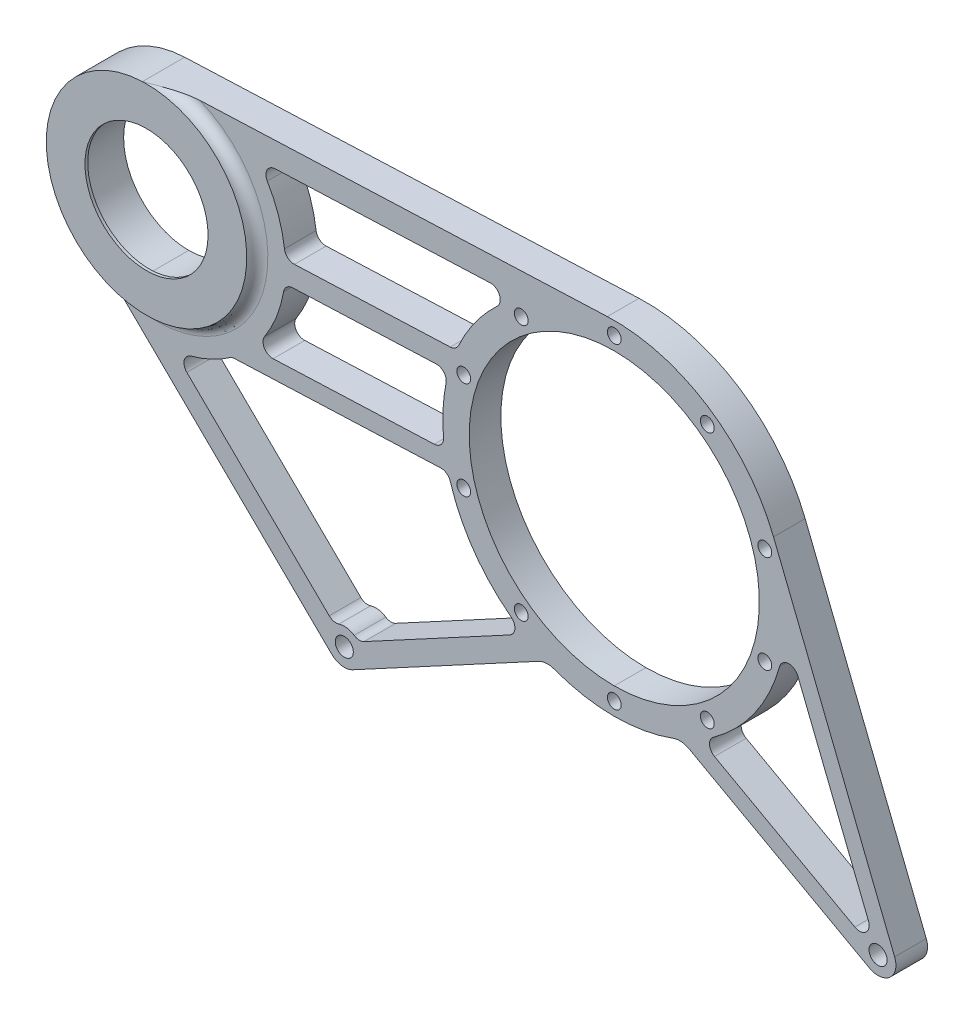
SolidWorks part; units mm, degrees
material "6061-T6 (SS)"
ref_plane "Front Plane" through (0, 0, 0) normal (0, 0, 1) x (1, 0, 0)
ref_plane "Top Plane" through (0, 0, 0) normal (0, 1, 0) x (1, 0, 0)
ref_plane "Right Plane" through (0, 0, 0) normal (1, 0, 0) x (0, 0, -1)
sketch "Sketch1" plane through (0, 0, 0) normal (0, 0, 1) x (1, 0, 0)
  line L0 (-114.3, 95.25) -> (-114.3, 107.95) construction
  line L1 (-280.8642, 163.1704) -> (-116.8043, 169.8118)
  line L2 (-304.7421, 101.1501) -> (-216.3071, 14.4521)
  line L3 (-13.0706, 21.4387) -> (-56.8054, 130.918)
  line L4 (-208.742, 13.3833) -> (-141.7118, 49.5504)
  line L5 (-22.1639, 13.4141) -> (-87.2342, 49.3665)
  circle A0 centre (-279.4, 127) radius 23.5
  circle A1 centre (-114.3, 95.25) radius 36 construction
  circle A2 centre (0, 0) radius 12.7 construction
  circle A3 centre (-228.6, 0) radius 12.7 construction
  circle A4 centre (-114.3, 107.95) radius 52.3875
  circle A5 centre (-19.05, 19.05) radius 3.2639
  circle A6 centre (-211.7995, 19.05) radius 3.2639
  circle A7 centre (-279.4, 127) radius 36.2
  arc A8 (-135.9521, 49.947) -> (-93.0137, 49.8118) centre (-114.3, 107.95) ccw
  arc A9 (-216.3071, 14.4521) -> (-208.742, 13.3833) centre (-211.7995, 19.05) ccw
  arc A10 (-22.1639, 13.4141) -> (-13.0706, 21.4387) centre (-19.05, 19.05) ccw
  arc A11 (-56.8054, 130.918) -> (-116.8043, 169.8118) centre (-114.3, 107.95) ccw
  arc A12 (-135.9521, 49.947) -> (-141.7118, 49.5504) centre (-138.3949, 43.4031) ccw
  arc A13 (-87.2342, 49.3665) -> (-93.0137, 49.8118) centre (-90.6122, 43.2526) ccw
  point P27 (-90.1176, 50.9555)
  point P28 (-138.831, 50.9555)
  dimension "D5" = 72
  dimension "D6" = 47
  dimension "D7" = 25.4
  dimension "D8" = 25.4
  dimension "D11" = 104.775
  dimension "D14" = 6.5278
  dimension "D15" = 6.5278
  dimension "D16" = 25.4
  dimension "D17" = 12.7
  dimension "D18" = 123.825
  dimension "D19" = 3.175
  dimension "D20" = 6.985
  dimension "D21" = 6.985
  dimension "D1" = 114.3
  dimension "D2" = 95.25
  dimension "D3" = 279.4
  dimension "D4" = 127
  dimension "D9" = 228.6
  dimension "D10" = 12.7
  dimension "D12" = 19.05
  dimension "D13" = 19.05
extrude "Boss-Extrude1" add sketch "Sketch1" along normal blind 11.43 contours A13 L5 A10 L3 A11 L1 A7 L2 A9 L4 A12 A8 A6 A5 A4 | A7 A0 region at (-168.693, 91.0379, 0) region at (-255.035, 152.3713, 0)
sketch "Sketch2" plane through (0, 0, 11.43) normal (0, 0, 1) x (1, 0, 0)
  circle A0 centre (-279.4, 127) radius 36.2
  circle A1 centre (-279.4, 127) radius 23.5
extrude "Boss-Extrude2" add sketch "Sketch2" along normal blind 3.81
fillet "Fillet1" radius 3.81 1 edges at (-245.6173, 113.9936, 11.43)
sketch "Sketch3" plane through (0, 0, 11.43) normal (0, 0, 1) x (1, 0, 0)
  line L0 (-114.3, 107.95) -> (-114.3, 165.1) construction
  circle A0 centre (-114.3, 107.95) radius 57.15 construction
  circle A1 centre (-114.3, 165.1) radius 2.5
  circle A2 centre (-80.7081, 154.1853) radius 2.5
  circle A3 centre (-59.9471, 125.6103) radius 2.5
  circle A4 centre (-59.9471, 90.2897) radius 2.5
  circle A5 centre (-80.7081, 61.7147) radius 2.5
  circle A6 centre (-114.3, 50.8) radius 2.5
  circle A7 centre (-147.8919, 61.7147) radius 2.5
  circle A8 centre (-168.6529, 90.2897) radius 2.5
  circle A9 centre (-168.6529, 125.6103) radius 2.5
  circle A10 centre (-147.8919, 154.1853) radius 2.5
  point P25 (-114.3, 107.95)
  dimension "D1" = 114.3
  dimension "D2" = 5
  dimension "D3" = 10
extrude "5mm Holes" cut sketch "Sketch3" against normal through all
sketch "Sketch4" plane through (0, 0, 15.24) normal (0, 0, 1) x (1, 0, 0)
  circle A0 centre (-279.4, 127) radius 22.225
  circle A1 centre (-279.4, 127) radius 23.5 construction
  circle A2 centre (-279.4, 127) radius 23.5
  dimension "D1" = 44.45
extrude "Boss-Extrude3" add sketch "Sketch4" against normal blind 1
sketch "Sketch5" plane through (0, 0, 11.43) normal (0, 0, 1) x (1, 0, 0)
  line L0 (-48.0193, 91.8071) -> (-22.5033, 27.9342)
  line L1 (-13.0706, 21.4387) -> (-56.8054, 130.918) construction
  line L2 (-78.1047, 51.5771) -> (-27.4356, 23.5816)
  line L3 (-22.1639, 13.4141) -> (-87.2342, 49.3665) construction
  line L4 (-236.7455, 156.0591) -> (-159.125, 159.2013)
  line L5 (-263.8382, 163.8596) -> (-116.8043, 169.8118) construction
  line L6 (-229.7856, 129.649) -> (-173.517, 131.9269)
  line L7 (-230.4174, 121.9972) -> (-178.6103, 124.0944)
  line L8 (-268.6449, 76.4329) -> (-217.2302, 26.028)
  line L9 (-204.6483, 24.2506) -> (-152.0143, 52.6499)
  line L10 (-292.5742, 89.2212) -> (-216.3071, 14.4521) construction
  line L11 (-208.742, 13.3833) -> (-141.7118, 49.5504) construction
  line L12 (-237.4937, 96.2899) -> (-179.3047, 98.6455)
  line L13 (-251.3498, 89.3738) -> (-177.0086, 92.3833)
  arc A0 (-175.0426, 119.9291) -> (-175.9673, 102.4457) centre (-114.3, 107.95) ccw construction
  circle A1 centre (-211.7995, 19.05) radius 6.4389 construction
  circle A2 centre (-19.05, 19.05) radius 6.4389 construction
  arc A3 (-54.6287, 91.4427) -> (-78.4387, 57.481) centre (-114.3, 107.95) cw
  arc A4 (-48.0193, 91.8071) -> (-54.6287, 91.4427) centre (-51.2626, 90.5115) ccw
  arc A5 (-27.4356, 23.5816) -> (-22.5033, 27.9342) centre (-25.7466, 26.6385) ccw
  arc A6 (-78.1047, 51.5771) -> (-78.4387, 57.481) centre (-76.4157, 54.634) cw
  arc A7 (-233.3928, 132.7086) -> (-253.1835, 88.7646) centre (-279.4, 127) ccw construction
  arc A8 (-292.5742, 89.2212) -> (-263.8382, 163.8596) centre (-279.4, 127) ccw construction
  arc A9 (-213.7352, 25.191) -> (-208.2383, 24.4145) centre (-211.7995, 19.05) cw
  arc A10 (-156.5977, 153.1613) -> (-170.4887, 133.9499) centre (-114.3, 107.95) ccw
  arc A11 (-175.0426, 119.9291) -> (-175.9673, 102.4457) centre (-114.3, 107.95) ccw
  arc A12 (-173.5263, 89.9112) -> (-151.5703, 58.5123) centre (-114.3, 107.95) ccw
  arc A13 (-239.6024, 150.7781) -> (-233.3928, 132.7086) centre (-279.4, 127) cw
  arc A14 (-233.7176, 119.1025) -> (-240.5609, 101.6865) centre (-279.4, 127) cw
  arc A15 (-240.5609, 101.6865) -> (-233.7176, 119.1025) centre (-279.4, 127) ccw construction
  arc A16 (-253.1835, 88.7646) -> (-267.1247, 82.2947) centre (-279.4, 127) cw
  arc A17 (-159.125, 159.2013) -> (-156.5977, 153.1613) centre (-158.9837, 155.7117) cw
  arc A18 (-173.517, 131.9269) -> (-170.4887, 133.9499) centre (-173.6583, 135.4165) ccw
  arc A19 (-229.7856, 129.649) -> (-233.3928, 132.7086) centre (-229.9269, 133.1386) cw
  arc A20 (-236.7455, 156.0591) -> (-239.6024, 150.7781) centre (-236.6043, 152.5695) ccw
  arc A21 (-179.3047, 98.6455) -> (-175.9673, 102.4457) centre (-179.446, 102.1352) ccw
  arc A22 (-178.6103, 124.0944) -> (-175.0426, 119.9291) centre (-178.4691, 120.6048) cw
  arc A23 (-230.4174, 121.9972) -> (-233.7176, 119.1025) centre (-230.2762, 118.5075) ccw
  arc A24 (-237.4937, 96.2899) -> (-240.5609, 101.6865) centre (-237.6349, 99.7796) cw
  arc A25 (-217.2302, 26.028) -> (-213.7352, 25.191) centre (-214.7852, 28.522) ccw
  arc A26 (-204.6483, 24.2506) -> (-208.2383, 24.4145) centre (-206.3067, 27.3242) cw
  arc A27 (-152.0143, 52.6499) -> (-151.5703, 58.5123) centre (-153.6727, 55.7236) ccw
  arc A28 (-177.0086, 92.3833) -> (-173.5263, 89.9112) centre (-176.8673, 88.8936) cw
  arc A29 (-251.3498, 89.3738) -> (-253.1835, 88.7646) centre (-251.2085, 85.8842) ccw
  arc A30 (-268.6449, 76.4329) -> (-267.1247, 82.2947) centre (-266.1999, 78.9268) cw
  arc A31 (-173.5263, 89.9112) -> (-170.4887, 133.9499) centre (-114.3, 107.95) ccw construction
  point P17 (-52.5701, 103.1988)
  point P23 (-83.2204, 54.4036)
  point P51 (-148.3837, 159.6362)
  point P54 (-171.3442, 132.0148)
  point P60 (-243.0732, 155.8029)
  point P63 (-175.5324, 98.7982)
  point P66 (-174.02, 124.2803)
  point P75 (-215.4925, 24.3245)
  point P78 (-206.7898, 23.0951)
  point P81 (-146.981, 55.3657)
  point P84 (-174.2524, 92.4948)
  point P90 (-273.3418, 81.0375)
  dimension "D1" = 123.825
  dimension "D2" = 12.8778
  dimension "D5" = 3.4925
  dimension "D6" = 6.35
  dimension "D14" = 3.4925
  dimension "D3" = 6.35
  dimension "D4" = 6.35
  dimension "D7" = 8.89
  dimension "D8" = 7.62
  dimension "D9" = 7.62
  dimension "D10" = 7.62
  dimension "D11" = 6.35
  dimension "D12" = 25.4
  dimension "D13" = 26.67
extrude "Cut-Extrude2" cut sketch "Sketch5" against normal through all both and the other way through all
ref_axis "Axis2" through (-279.4, 127, 14.24) along (0, 0, -1)
ref_axis "Axis1" through (-114.3, 107.95, 11.43) along (0, 0, -1)
ref_plane "Plane1" through (-114.3, 0, 0) normal (1, 0, 0) x (0, 0, -1)
ref_plane "Plane2" through (-279.4, 0, 0) normal (1, 0, 0) x (0, 0, -1)
ref_plane "Plane3" through (0, 0, 5.715) normal (0, 0, -1) x (-1, 0, 0)
ref_plane "Plane4" through (0, 0, 7.12) normal (0, 0, -1) x (-1, 0, 0)
split line "Split Line1"
split line "Split Line2"
sketch "Sketch6" plane through (0, 0, 5.715) normal (0, 0, -1) x (-1, 0, 0)
  circle A1 centre (114.3, 107.95) radius 52.3875 construction
sketch "Sketch7" plane through (0, 0, 7.12) normal (0, 0, -1) x (-1, 0, 0)
  circle A0 centre (279.4, 127) radius 23.5
